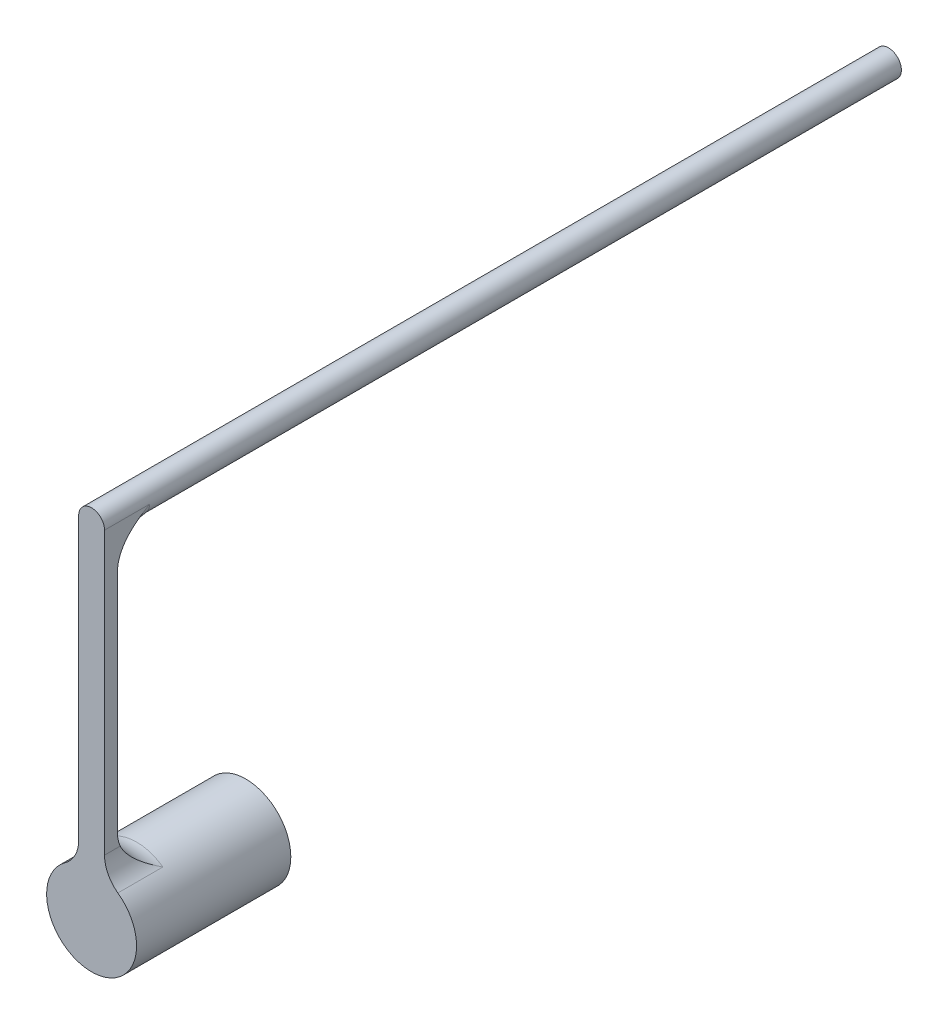
SolidWorks part; units mm, degrees
ref_plane "前视基准面" through (0, 0, 0) normal (0, 0, 1) x (1, 0, 0)
ref_plane "上视基准面" through (0, 0, 0) normal (0, 1, 0) x (1, 0, 0)
ref_plane "右视基准面" through (0, 0, 0) normal (1, 0, 0) x (0, 0, -1)
other "Configuration Table"
sketch "草图1" plane through (0, 0, 0) normal (0, 0, 1) x (1, 0, 0)
  circle A0 centre (0, 0) radius 7
extrude "凸台-拉伸1" add sketch "草图1" along normal blind 22
sketch "草图2" plane through (0, 0, 22) normal (0, 0, 1) x (1, 0, 0)
  line L0 (0, 0) -> (0, 53.5316) construction
  line L1 (-2.0095, 0) -> (-2.0095, 53.5316)
  line L2 (2.0095, 0) -> (2.0095, 53.5316)
  circle A0 centre (0, 0) radius 7
  arc A1 (-2.0095, 0) -> (2.0095, 0) centre (0, 0) ccw
  arc A2 (2.0095, 53.5316) -> (-2.0095, 53.5316) centre (0, 53.5316) ccw
  point P3 (0, 26.7658)
  circle M1 centre (0, 0) radius 7
extrude "凸台-拉伸2" add sketch "草图2" along normal blind 2 contours A1 L1 L2 M1 | L2 A2 L1 A0 M1 | L1 A1 L2 A0 M1 region at (0, -2.2054, 22) region at (0, 2.6508, 22) region at (0, 31.0082, 22)
fillet "圆角1" radius 5 1 edges at (0, 7, 22)
fillet "圆角2" radius 5 2 edges at (2.0095, 6.7054, 20.5) (-2.0095, 6.7054, 20.5)
sketch "草图3" plane through (0, 0, 22) normal (0, 0, -1) x (-1, 0, 0)
  circle A0 centre (0, 53.5316) radius 2.0095
extrude "凸台-拉伸3" add sketch "草图3" along normal blind 122
fillet "圆角3" radius 5 1 edges at (0, 51.5221, 22)
